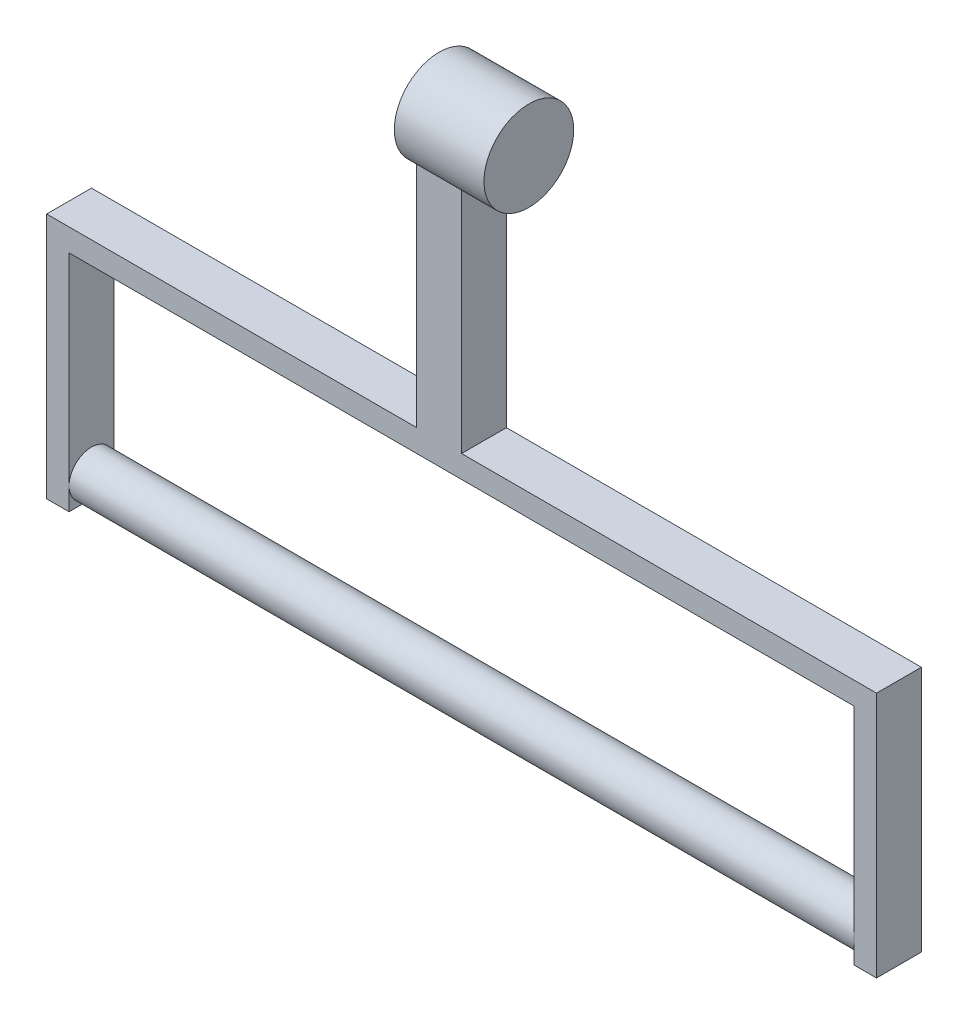
SolidWorks part; units mm, degrees
ref_plane "前视基准面" through (0, 0, 0) normal (0, 0, 1) x (1, 0, 0)
ref_plane "上视基准面" through (0, 0, 0) normal (0, 1, 0) x (1, 0, 0)
ref_plane "右视基准面" through (0, 0, 0) normal (1, 0, 0) x (0, 0, -1)
sketch "草图1" plane through (0, 0, 0) normal (0, 0, 1) x (1, 0, 0)
  line L0 (-10, 0) -> (-10, -60)
  line L1 (-10, -60) -> (10, -60)
  line L2 (10, -60) -> (10, 0)
  circle A0 centre (0, 0) radius 10
extrude "凸台-拉伸1" add sketch "草图1" along normal blind 10 contours A0 | A0 L0 L1 L2 region at (0, -33.8792, 0) region at (0, 0, 0)
extrude "凸台-拉伸2" add sketch "草图1<4>" against normal blind 10 contours A0 region at (0, 0, 0)
sketch "草图1<4>" plane through (0, 0, 0) normal (0, 0, 1) x (1, 0, 0) same geometry as "草图1"
sketch "草图2" plane through (0, -60, 0) normal (0, -1, 0) x (1, 0, 0)
  line L0 (0, 0) -> (-87.5, 0)
  line L1 (0, 0) -> (87.5, 0)
  line L2 (87.5, 0) -> (87.5, 10)
  line L3 (87.5, 10) -> (-87.5, 10)
  line L4 (-87.5, 0) -> (-87.5, 10)
  line L5 (-87.5, 10) -> (-92.5, 10)
  line L6 (-92.5, 10) -> (-92.5, 0)
  line L7 (-92.5, 0) -> (-87.5, 0)
  line L8 (87.5, 0) -> (92.5, 0)
  line L9 (92.5, 0) -> (92.5, 10)
  line L10 (92.5, 10) -> (87.5, 10)
extrude "凸台-拉伸6" add sketch "草图2" along normal blind 55 separate body contours L6 L7 L4 L5 | L9 L10 L2 L8 region at (-90, -60, 5) region at (90, -60, 5)
extrude "凸台-拉伸7" add sketch "草图2<5>" along normal blind 5 contours L4 L0 L8 L3 | L2 L3 L6 L1 | L8 L5 L6 L7 region at (0, -60, 5) region at (-90, -60, 5)
sketch "草图2<5>" plane through (0, -60, 0) normal (0, -1, 0) x (1, 0, 0) same geometry as "草图2"
sketch "草图5" plane through (-87.5, 0, 0) normal (1, 0, 0) x (0, 0, -1)
  line L0 (0, -115) -> (-10, -105)
  line L1 (-10, -115) -> (-10, -60) construction
  line L2 (-10, -105) -> (0, -105)
  line L3 (0, -115) -> (0, -60) construction
  line L4 (0, -105) -> (-10, -115)
  circle A0 centre (-5, -110) radius 5
extrude "凸台-拉伸8" add sketch "草图5" along normal blind 175 contours L4 A0 L0 | L0 A0 L4 | L4 A0 L0 | A0 L4 L0 region at (-87.5, -113.0011, 5) region at (-87.5, -110, 1.9989) region at (-87.5, -110, 8.0011) region at (-87.5, -106.9989, 5)
sketch "草图6" plane through (0, 0, -10) normal (0, 0, -1) x (-1, 0, 0)
  line L0 (0, 0) -> (0, -10)
  line L1 (0, -10) -> (-10, -10)
  line L2 (-10, -60) -> (-10, 0) construction
  line L3 (0, -10) -> (10, -10)
  line L4 (10, 0) -> (10, -60) construction
  line L5 (-10, -10) -> (-10, 10)
  line L6 (-10, 10) -> (10, 10)
  line L7 (10, 10) -> (10, -10)
  arc A0 (-10, 0) -> (10, 0) centre (0, 0) ccw construction
  circle M6 centre (0, 0) radius 10
extrude "切除-拉伸1" cut sketch "草图6" against normal blind 175 contours M6 | L1 L5 L6 L7 L3 region at (6.8711, -6.8711, -10) body kept at (-87.5, -65, 0)
sketch "草图7" plane through (0, -10, 0) normal (0, 1, 0) x (1, 0, 0)
  line L0 (0, 0) -> (0, -10)
  line L1 (10, -10) -> (-10, -10) construction
  line L2 (0, -10) -> (10, -10)
  line L3 (10, -10) -> (10, 0)
  line L4 (10, 0) -> (0, 0)
extrude "切除-拉伸2" cut sketch "草图7" against normal blind 50
sketch "草图8" plane through (0, 0, 0) normal (1, 0, 0) x (0, 0, -1)
  line L0 (-10, -10) -> (-10, 0)
  line L1 (-10, 0) -> (0, 0)
  line L2 (0, 0) -> (0, -10)
  circle A0 centre (-5, 0) radius 10
  line M1 (0, -10) -> (-10, -10)
extrude "凸台-拉伸9" add sketch "草图8" against normal blind 10 contours L0 A0 L2 L1 | A0 L2 M1 | A0 L0 M1 | L2 A0 L0 L1 region at (0, -9.6032, 8.7674) region at (0, 2.0977, 5) region at (0, -4.7912, 5) region at (0, -9.6032, 1.2326)
extrude "凸台-拉伸10" add sketch "草图8<3>" along normal blind 10 contours L2 A0 L0 L1 | L0 A0 L2 L1 region at (0, 2.0977, 5) region at (0, -4.7912, 5)
sketch "草图8<3>" plane through (0, 0, 0) normal (1, 0, 0) x (0, 0, -1) same geometry as "草图8"
